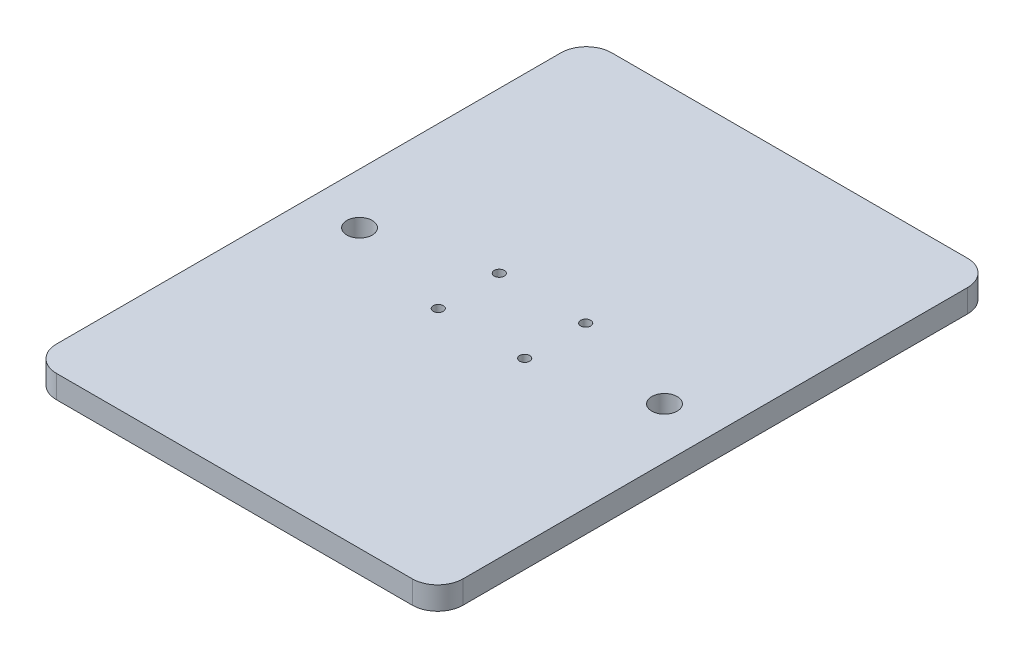
SolidWorks part; units mm, degrees
ref_plane "Front Plane" through (0, 0, 0) normal (0, 0, 1) x (1, 0, 0)
ref_plane "Top Plane" through (0, 0, 0) normal (0, 1, 0) x (1, 0, 0)
ref_plane "Right Plane" through (0, 0, 0) normal (1, 0, 0) x (0, 0, -1)
sketch "Sketch1" plane through (0, 12.7625, 0) normal (0, 1, 0) x (1, 0, 0)
  line L0 (0, 69.3699) -> (-12.5, 69.3699) construction
  line L1 (-44.45, -69.3699) -> (44.45, -69.3699)
  line L2 (-50.8, -63.0199) -> (-50.8, 63.0199)
  line L3 (-44.45, 69.3699) -> (44.45, 69.3699)
  line L4 (50.8, -63.0199) -> (50.8, 63.0199)
  line L5 (-50.8, -69.3699) -> (50.8, 69.3699) construction
  line L6 (-50.8, 69.3699) -> (50.8, -69.3699) construction
  line L8 (-38.1, 0) -> (38.1, 0) construction
  arc A0 (44.45, -69.3699) -> (50.8, -63.0199) centre (44.45, -63.0199) ccw
  arc A1 (-44.45, -69.3699) -> (-50.8, -63.0199) centre (-44.45, -63.0199) cw
  arc A2 (-50.8, 63.0199) -> (-44.45, 69.3699) centre (-44.45, 63.0199) cw
  arc A3 (44.45, 69.3699) -> (50.8, 63.0199) centre (44.45, 63.0199) cw
  circle A4 centre (10.795, 7.62) radius 1.25 construction
  circle A5 centre (10.795, -7.62) radius 1.25 construction
  circle A6 centre (-10.795, -7.62) radius 1.25 construction
  circle A7 centre (-10.795, 7.62) radius 1.25 construction
  circle A8 centre (10.795, 7.62) radius 1.25
  circle A9 centre (10.795, -7.62) radius 1.25
  circle A10 centre (-10.795, -7.62) radius 1.25
  circle A11 centre (-10.795, 7.62) radius 1.25
  circle A13 centre (38.1, 0) radius 3.175
  circle A15 centre (-38.1, 0) radius 3.175
  point P0 (0, 0)
  point P32 (0, 0)
  point P33 (0, 0)
  dimension "D2" = 6.35
  dimension "D4" = 6.35
  dimension "D1" = 101.6
  dimension "D3" = 76.2
extrude "Boss-Extrude1" add sketch "Sketch1" along normal blind 5.715
